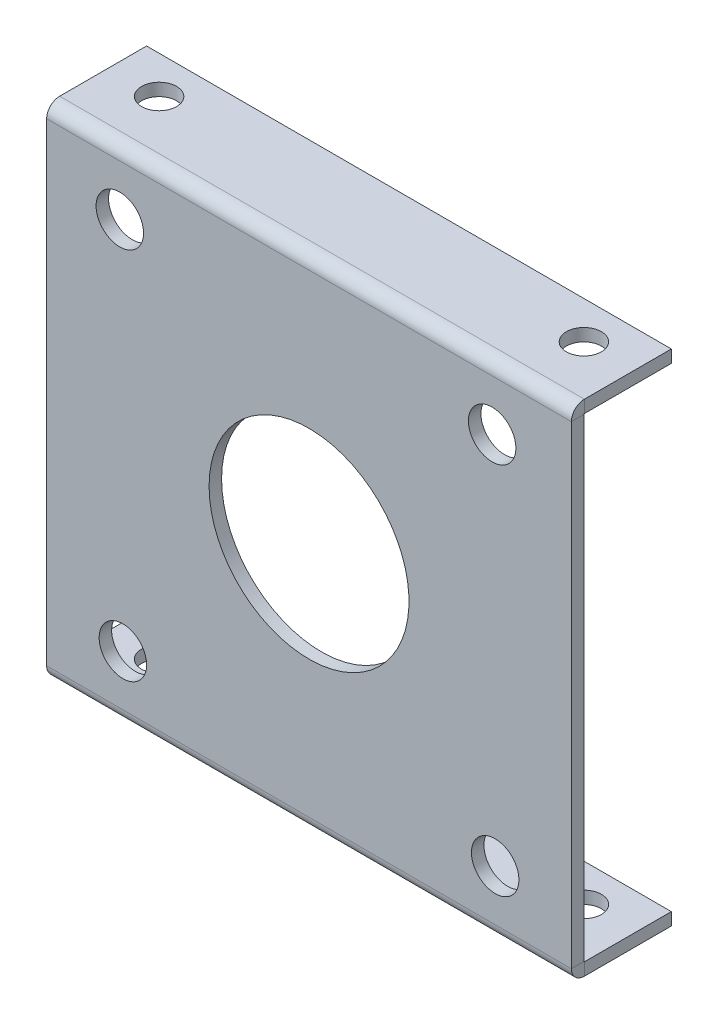
SolidWorks part; units mm, degrees
note: The reader was unsure of these and kept them because the rebuilt part matched: flange length of "Edge-Flange1", "Edge-Flange2".
material "ASTM A36 Steel"
ref_plane "Front Plane" through (0, 0, 0) normal (0, 0, 1) x (1, 0, 0)
ref_plane "Top Plane" through (0, 0, 0) normal (0, 1, 0) x (1, 0, 0)
ref_plane "Right Plane" through (0, 0, 0) normal (1, 0, 0) x (0, 0, -1)
sketch "Sketch1" plane through (0, 0, 0) normal (0, 0, 1) x (1, 0, 0)
  line L1 (-105, -100) -> (105, -100)
  line L2 (-105, -100) -> (-105, 100)
  line L3 (-105, 100) -> (105, 100)
  line L4 (105, -100) -> (105, 100)
  line L5 (-105, -100) -> (105, 100) construction
  line L6 (-105, 100) -> (105, -100) construction
  point P0 (0, 0)
  dimension "D1" = 210
  dimension "D2" = 200
base flange "Base-Flange1" sketch "Sketch1" thickness 5 reverse thickness direction no parameters "D1"=0.2
edge flange "Edge-Flange1" sketch "Sketch8" flange angle 90 flange length 40 flange position material inside bend radius 0.2 thickness 5 relief rectangular parameters "D6"=10
sketch "Sketch8" plane through (0, 100, -5) normal (0, -1, 0) x (-1, 0, 0)
  line L2 (-105, 0) -> (-105, 35)
  line L3 (-105, 35) -> (105, 35)
  line L4 (105, 35) -> (105, 0)
  line L9 (105, 0) -> (-105, 0) construction
  line L10 (105, 0) -> (-105, 0)
bend "EdgeBend1" bend radius 0.2 bend angle 90 parameters "D5"=1
edge flange "Edge-Flange2" sketch "Sketch11" flange angle 90 flange length 40 flange position material inside bend radius 0.2 thickness 5 relief rectangular parameters "D6"=10
sketch "Sketch11" plane through (0, -100, -5) normal (0, -1, 0) x (-1, 0, 0)
  line L2 (-105, 0) -> (-105, 35)
  line L3 (-105, 35) -> (105, 35)
  line L4 (105, 35) -> (105, 0)
  line L7 (105, 0) -> (-105, 0) construction
  line L8 (105, 0) -> (-105, 0)
bend "EdgeBend2" bend radius 0.2 bend angle 90 parameters "D5"=2
sketch "Sketch12" plane through (0, 0, 0) normal (0, 0, 1) x (1, 0, 0)
  circle A0 centre (0, 0) radius 40
  dimension "D1" = 80
extrude "Cut-Extrude1" cut sketch "Sketch12" against normal through all both and the other way through all normal cut yes
sketch "Sketch13" plane through (0, 0, 0) normal (0, 0, 1) x (1, 0, 0)
  line L0 (-105, 94.8) -> (-105, -94.8) construction
  line L1 (-105, -100) -> (105, -100) construction
  circle A0 centre (73.283, 74.495) radius 9.5
  circle A1 centre (-75.717, 74.495) radius 9.5
  circle A2 centre (-74.5, -74.5) radius 9.5
  circle A3 centre (74.5, -74.5) radius 9.5
  point P0 (0, 0)
  dimension "D3" = 19
  dimension "D4" = 19
  dimension "D5" = 19
  dimension "D6" = 19
  dimension "D7" = 149
  dimension "D8" = 30.5
  dimension "D9" = 25.5
  dimension "D10" = 25.5
  dimension "D1" = 149
  dimension "D2" = 149
extrude "Cut-Extrude2" cut sketch "Sketch13" against normal through all both and the other way through all normal cut yes
sketch "Sketch14" plane through (0, -100, 0) normal (0, -1, 0) x (-1, 0, 0)
  line L0 (-105, 40) -> (-105, 5.2) construction
  line L1 (105, 5.2) -> (105, 40) construction
  line L2 (105, 40) -> (-105, 40) construction
  circle A0 centre (85, 25) radius 7
  circle A1 centre (-85, 25) radius 7
  dimension "D1" = 14
  dimension "D2" = 14
  dimension "D3" = 20
  dimension "D4" = 20
  dimension "D5" = 15
  dimension "D6" = 15
extrude "Cut-Extrude3" cut sketch "Sketch14" against normal through all both and the other way through all normal cut yes
sketch "Bend-Lines1" [suppressed] plane through (0, 0, 0) normal (0, 1, 0) x (1, 0, 0)
sketch "Bounding-Box1" [suppressed] plane through (0, 0, 0) normal (0, 1, 0) x (1, 0, 0)
sheet metal parameters "Sheet-Metal1" thickness 5 parameters "D1"=0.2
flat pattern "Flat-Pattern1" [suppressed]
sketch "Bend-Lines2" plane through (0, 0, 0) normal (0, 1, 0) x (1, 0, 0)
sketch3d "Bounding-Box2" [suppressed]
  line L0 (-85, 100, 0) -> (-85, -100, 0) construction
  line L1 (85, 100, 0) -> (85, -100, 0) construction
  line L2 (-85, 100, 0) -> (85, 100, 0) construction
  line L3 (-85, -100, 0) -> (85, -100, 0) construction
sheet metal parameters "Sheet-Metal2" thickness 5 parameters "D1"=0.2
flat pattern "Flat-Pattern1"
sketch "Bend-Lines2" plane through (0, 0, 0) normal (0, 0, 1) x (1, 0, 0)
  line L0 (85, 96.9206) -> (-85, 96.9206) construction
  line L1 (85, 96.9206) -> (-85, 96.9206) construction
sketch3d "Bounding-Box2" [suppressed]
  line L0 (85, 143.8412, 0) -> (85, -100, 0) construction
  line L1 (-85, 143.8412, 0) -> (-85, -100, 0) construction
  line L2 (85, 143.8412, 0) -> (-85, 143.8412, 0) construction
  line L3 (85, -100, 0) -> (-85, -100, 0) construction
bend of the flat pattern "Flatten-<EdgeBend1>1"
sheet metal parameters "Sheet-Metal3" thickness 5 parameters "D1"=0.2
flat pattern "Flat-Pattern1"
sketch "Bend-Lines2" plane through (0, 0, 0) normal (0, 0, 1) x (1, 0, 0)
  line L0 (85, 96.9206) -> (-85, 96.9206) construction
  line L1 (85, 96.9206) -> (-85, 96.9206) construction
  line L2 (-85, -96.9206) -> (85, -96.9206) construction
  line L3 (-85, -96.9206) -> (85, -96.9206) construction
sketch3d "Bounding-Box2" [suppressed]
  line L0 (85, 143.8412, 0) -> (85, -143.8412, 0) construction
  line L1 (-85, 143.8412, 0) -> (-85, -143.8412, 0) construction
  line L2 (85, 143.8412, 0) -> (-85, 143.8412, 0) construction
  line L3 (85, -143.8412, 0) -> (-85, -143.8412, 0) construction
bend of the flat pattern "Flatten-<EdgeBend1>1"
bend of the flat pattern "Flatten-<EdgeBend2>1"
sheet metal parameters "Sheet-Metal4" thickness 5 parameters "D1"=0.2
flat pattern "Flat-Pattern1"
sketch "Bend-Lines2" plane through (0, 0, 0) normal (0, 0, 1) x (1, 0, 0)
  line L0 (85, 96.9206) -> (-85, 96.9206) construction
  line L1 (85, 96.9206) -> (-85, 96.9206) construction
  line L2 (-85, -96.9206) -> (85, -96.9206) construction
  line L3 (-85, -96.9206) -> (85, -96.9206) construction
sketch3d "Bounding-Box2" [suppressed]
  line L0 (85, 143.8412, 0) -> (85, -143.8412, 0) construction
  line L1 (-85, 143.8412, 0) -> (-85, -143.8412, 0) construction
  line L2 (85, 143.8412, 0) -> (-85, 143.8412, 0) construction
  line L3 (85, -143.8412, 0) -> (-85, -143.8412, 0) construction
bend of the flat pattern "Flatten-<EdgeBend1>1"
bend of the flat pattern "Flatten-<EdgeBend2>1"
sheet metal parameters "Sheet-Metal5" thickness 5 parameters "D1"=0.2
flat pattern "Flat-Pattern1"
sketch "Bend-Lines2" plane through (0, 0, 0) normal (0, 0, 1) x (1, 0, 0)
  line L0 (85, 96.9206) -> (-85, 96.9206) construction
  line L1 (85, 96.9206) -> (-85, 96.9206) construction
  line L2 (-85, -96.9206) -> (85, -96.9206) construction
  line L3 (-85, -96.9206) -> (85, -96.9206) construction
sketch3d "Bounding-Box2" [suppressed]
  line L0 (85, 143.8412, 0) -> (85, -143.8412, 0) construction
  line L1 (-85, 143.8412, 0) -> (-85, -143.8412, 0) construction
  line L2 (85, 143.8412, 0) -> (-85, 143.8412, 0) construction
  line L3 (85, -143.8412, 0) -> (-85, -143.8412, 0) construction
bend of the flat pattern "Flatten-<EdgeBend1>1"
bend of the flat pattern "Flatten-<EdgeBend2>1"
sheet metal parameters "Sheet-Metal6" thickness 5 parameters "D1"=0.2
flat pattern "Flat-Pattern1"
sketch "Bend-Lines2" plane through (0, 0, 0) normal (0, 0, 1) x (1, 0, 0)
  line L0 (105, 96.9206) -> (-105, 96.9206) construction
  line L1 (105, 96.9206) -> (-105, 96.9206) construction
  line L2 (-105, -96.9206) -> (105, -96.9206) construction
  line L3 (-105, -96.9206) -> (105, -96.9206) construction
sketch3d "Bounding-Box2" [suppressed]
  line L0 (105, 133.8412, 0) -> (105, -133.8412, 0) construction
  line L1 (-105, 133.8412, 0) -> (-105, -133.8412, 0) construction
  line L2 (105, 133.8412, 0) -> (-105, 133.8412, 0) construction
  line L3 (105, -133.8412, 0) -> (-105, -133.8412, 0) construction
bend of the flat pattern "Flatten-<EdgeBend1>1"
bend of the flat pattern "Flatten-<EdgeBend2>1"
